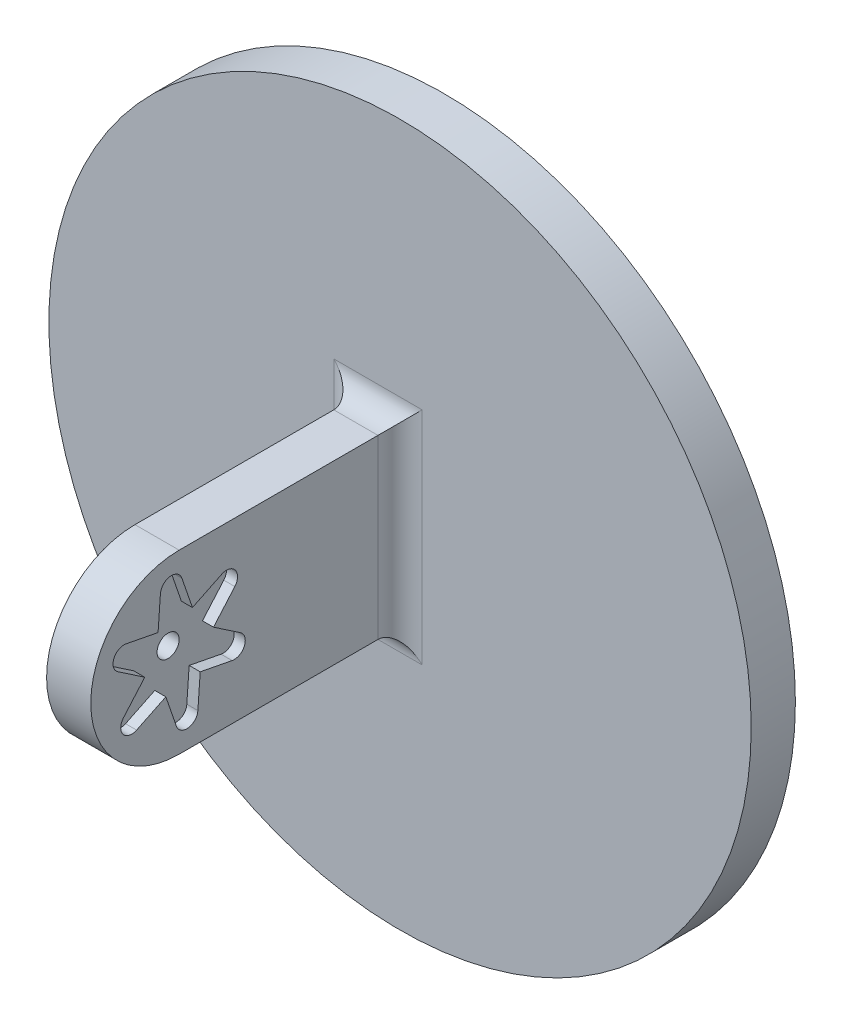
SolidWorks part; units mm, degrees
material "ABS"
ref_plane "Front Plane" through (0, 0, 0) normal (0, 0, 1) x (1, 0, 0)
ref_plane "Top Plane" through (0, 0, 0) normal (0, 1, 0) x (1, 0, 0)
ref_plane "Right Plane" through (0, 0, 0) normal (1, 0, 0) x (0, 0, -1)
sketch "Sketch1" plane through (0, 0, 0) normal (0, 0, 1) x (1, 0, 0)
  circle A0 centre (0, 0) radius 79.4804
  dimension "D1" = 158.9607
extrude "Boss-Extrude1" add sketch "Sketch1" along normal blind 10
sketch "Sketch2" plane through (0, 0, 10) normal (0, 0, 1) x (1, 0, 0)
  line L0 (0, 0) -> (0, -20)
  line L1 (0, -20) -> (-10, -20)
  line L2 (-10, -20) -> (-10, 20)
  line L3 (-10, 20) -> (0, 20)
  line L4 (0, 20) -> (0, 0)
  dimension "D1" = 40
  dimension "D2" = 10
  dimension "D3" = 20
extrude "Boss-Extrude2" add sketch "Sketch2" along normal blind 70
fillet "Fillet3" radius 5 4 edges at (-10, 0, 10) (-5, -20, 10) (-5, 20, 10) (0, 0, 10)
sketch "Sketch4" plane through (0, 0, 0) normal (0, 0, -1) x (-1, 0, 0)
  line L0 (-9.1215, 10.9003) -> (-6.7939, 3.9225)
  line L1 (-6.7939, 3.9225) -> (-14.0007, 2.4494)
  line L2 (-4.8791, 13.3496) -> (0, 7.845)
  line L3 (0, 7.845) -> (4.8791, 13.3496)
  line L4 (9.1215, 10.9003) -> (6.7939, 3.9225)
  line L5 (6.7939, 3.9225) -> (14.0007, 2.4494)
  line L6 (-14.0007, -2.4494) -> (-6.7939, -3.9225)
  line L7 (-6.7939, -3.9225) -> (-9.1215, -10.9003)
  line L8 (-4.8791, -13.3496) -> (0, -7.845)
  line L9 (0, -7.845) -> (4.8791, -13.3496)
  line L10 (9.1215, -10.9003) -> (6.7939, -3.9225)
  line L11 (6.7939, -3.9225) -> (14.0007, -2.4494)
  arc A0 (14.0007, 2.4494) -> (14.0007, -2.4494) centre (13.5, 0) cw
  arc A1 (4.8791, 13.3496) -> (9.1215, 10.9003) centre (6.75, 11.6913) cw
  arc A2 (-9.1215, 10.9003) -> (-4.8791, 13.3496) centre (-6.75, 11.6913) cw
  arc A3 (-14.0007, -2.4494) -> (-14.0007, 2.4494) centre (-13.5, 0) cw
  arc A4 (-9.1215, -10.9003) -> (-4.8791, -13.3496) centre (-6.75, -11.6913) ccw
  arc A5 (4.8791, -13.3496) -> (9.1215, -10.9003) centre (6.75, -11.6913) ccw
sketch "Sketch7" plane through (0, 0, 0) normal (1, 0, 0) x (0, 0, -1)
  circle A0 centre (-60, 0) radius 2.5
extrude "Cut-Extrude4" cut sketch "Sketch7" against normal through all
sketch "Sketch9" plane through (0, 0, 0) normal (1, 0, 0) x (0, 0, -1)
  line L0 (-64.2396, 13.5663) -> (-64.7683, 6.2295)
  line L1 (-64.7683, 6.2295) -> (-71.9885, 7.6351)
  line L2 (-59.3821, 14.1999) -> (-56.9892, 7.2442)
  line L3 (-56.9892, 7.2442) -> (-50.3711, 10.4548)
  line L4 (-73.8686, 3.1115) -> (-67.7791, -1.0147)
  line L5 (-67.7791, -1.0147) -> (-72.6064, -6.5648)
  line L6 (-69.6289, -10.4548) -> (-63.0108, -7.2442)
  line L7 (-63.0108, -7.2442) -> (-60.6179, -14.1999)
  line L8 (-55.7604, -13.5663) -> (-55.2317, -6.2295)
  line L9 (-55.2317, -6.2295) -> (-48.0115, -7.6351)
  line L10 (-46.1314, -3.1115) -> (-52.2209, 1.0147)
  line L11 (-52.2209, 1.0147) -> (-47.3936, 6.5648)
  arc A0 (-50.3711, 10.4548) -> (-47.3936, 6.5648) centre (-49.2799, 8.2055) cw
  arc A1 (-46.1314, -3.1115) -> (-48.0115, -7.6351) centre (-47.5338, -5.1811) cw
  arc A2 (-55.7604, -13.5663) -> (-60.6179, -14.1999) centre (-58.2539, -13.3866) cw
  arc A3 (-69.6289, -10.4548) -> (-72.6064, -6.5648) centre (-70.7201, -8.2055) cw
  arc A4 (-73.8686, 3.1115) -> (-71.9885, 7.6351) centre (-72.4662, 5.1811) cw
  arc A5 (-64.2396, 13.5663) -> (-59.3821, 14.1999) centre (-61.7461, 13.3866) cw
extrude "Cut-Extrude6" cut sketch "Sketch9" against normal blind 2.5
fillet "Fillet5" 2 edges at (-5, -20, 80) (-5, 20, 80) type full round first side face at (-5, -20, 47.5) second side face at (-5, 20, 47.5) middle face at (-5, 0, 80)
extrude "Cut-Extrude7" cut sketch "Sketch4" against normal blind 2.5
